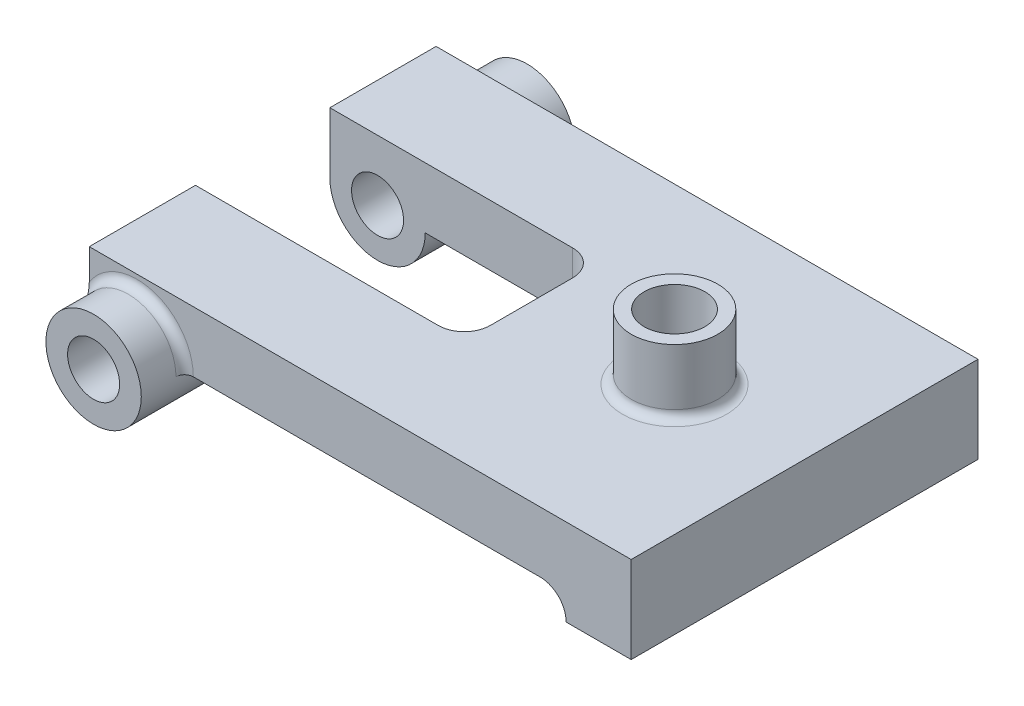
SolidWorks part; units mm, degrees
note: The reader was unsure of these and kept them because the rebuilt part matched: shared geometry of "Sketch1<5>", "Sketch4<2>".
ref_plane "Front Plane" through (0, 0, 0) normal (0, 0, 1) x (1, 0, 0)
ref_plane "Top Plane" through (0, 0, 0) normal (0, 1, 0) x (1, 0, 0)
ref_plane "Right Plane" through (0, 0, 0) normal (1, 0, 0) x (0, 0, -1)
sketch "Sketch1" plane through (0, 0, 0) normal (0, 0, 1) x (1, 0, 0)
  line L0 (0, 20) -> (125, 20)
  line L1 (125, 20) -> (125, 0)
  line L2 (125, 0) -> (110, 0)
  line L4 (103.7898, 5.9963) -> (22, 5.9963)
  line L5 (0, 5.9963) -> (0, 20)
  line L6 (47.6289, 0) -> (-23.7865, 0) construction
  line L7 (0, 29.7149) -> (0, -38.1767) construction
  circle A0 centre (11, 5.9963) radius 11
  circle A1 centre (11, 5.9963) radius 6
  arc A2 (103.7898, 5.9963) -> (110, 0) centre (104, 0) cw
  point P15 (0, 0)
  dimension "D4" = 22
  dimension "D6" = 5.9963
  dimension "D3" = 6
  dimension "D7" = 12
  dimension "D1" = 110
  dimension "D2" = 125
  dimension "D5" = 20
extrude "Boss-Extrude3" add sketch "Sketch1" along normal mid plane 80 contours L4 A2 L2 L1 L0 L5 A0
extrude "Boss-Extrude4" add sketch "Sketch1<5>" along normal mid plane 100 contours A0 A1
sketch "Sketch1<5>" plane through (0, 0, 0) normal (0, 0, 1) x (1, 0, 0) same geometry as "Sketch1"
sketch "Sketch3" plane through (0, 0, 0) normal (-1, 0, 0) x (0, 0, 1)
  line L0 (40, 20) -> (-40, 20) construction
  line L1 (-15.5, 20) -> (15.5, 20)
  line L2 (-15.5, 20) -> (-15.5, -5.0037)
  line L3 (-15.5, -5.0037) -> (15.5, -5.0037)
  line L4 (15.5, 20) -> (15.5, -5.0037)
  line L5 (-50, -5.0037) -> (50, -5.0037) construction
  line L6 (0, -0.6216) -> (0, -15.3994) construction
  point P10 (0, 0)
  point P12 (0, -5.0037)
  dimension "D1" = 31
extrude "Cut-Extrude1" cut sketch "Sketch3" against normal blind 62
sketch "Sketch4" plane through (0, 20, 0) normal (0, 1, 0) x (1, 0, 0)
  line L0 (125, -40) -> (125, 40) construction
  line L1 (62, -15.5) -> (62, 15.5) construction
  circle A0 centre (95, 0) radius 10
  circle A1 centre (95, 0) radius 7
  point P7 (0, 0)
  point P8 (62, 0)
  point P9 (0, 0)
  dimension "D1" = 20
  dimension "D2" = 14
  dimension "D3" = 30
extrude "Boss-Extrude5" add sketch "Sketch4" along normal blind 15
fillet "Fillet1" radius 2 3 edges at (95, 20, 10) (11, 16.9963, -40) (11, 16.9963, 40)
fillet "Fillet2" radius 6 2 edges at (62, 12.9982, 15.5) (62, 12.9982, -15.5)
extrude "Cut-Extrude2" cut sketch "Sketch4<2>" against normal blind 15 contours A1
sketch "Sketch4<2>" plane through (0, 20, 0) normal (0, 1, 0) x (1, 0, 0) same geometry as "Sketch4"
